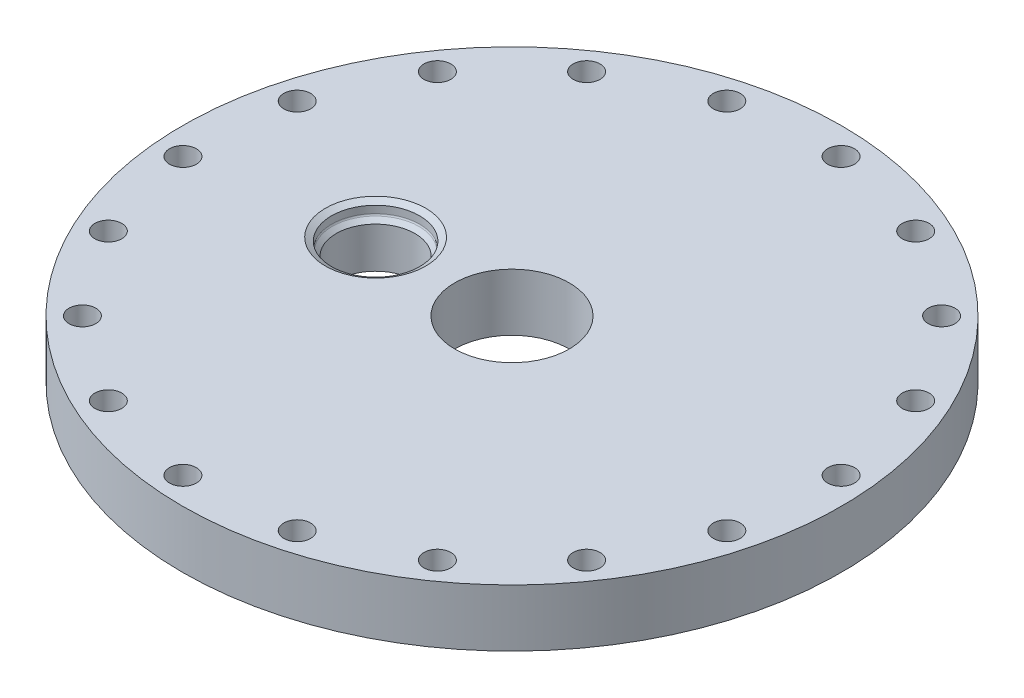
SolidWorks part; units mm, degrees
note: '?' marks a value the reader was unsure of.
material "7075-T6, Plate (SS)"
ref_plane "Front Plane" through (0, 0, 0) normal (0, 0, 1) x (1, 0, 0)
ref_plane "Top Plane" through (0, 0, 0) normal (0, 1, 0) x (1, 0, 0)
ref_plane "Right Plane" through (0, 0, 0) normal (1, 0, 0) x (0, 0, -1)
sketch "Top Plate Diameter" plane through (0, 0, 0) normal (0, 1, 0) x (1, 0, 0)
  circle A0 centre (0, 0) radius 73.025
  dimension "D1" = 146.05
extrude "Top Plate Extrude" add sketch "Top Plate Diameter" along normal blind 12.7
ref_axis "Center of Top Plate" through (0, 12.7, 0) along (0, -1, 0)?
sketch "Fuel Port Clearance Diameter" plane through (0, 12.7, 0) normal (0, 1, 0) x (1, 0, 0)
  circle A0 centre (0, 0) radius 12.7
  dimension "D1" = 25.4
extrude "Fuel Port Clearance Hole" cut sketch "Fuel Port Clearance Diameter" against normal through all
hole_wizard "3/4-16 Tapped LOX Port" [suppressed] positions "3DSketch3" profile "Sketch6" tap size "3/4-16" standard "Ansi Inch"
sketch3d "3DSketch3"
  line L0 (0, 0, 0) -> (0, 37.9824, 0) construction
  point P0 (-30.226, 8.89, 0)
  dimension "D2" = 30.226
sketch "Sketch6" plane through (-30.226, 8.89, 0) normal (1, 0, 0) x (0, 0, 1)
  line L0 (0, 0) -> (0, 17.9463)
  line L1 (0, 17.9463) -> (8.7312, 12.7)
  line L2 (8.7312, 12.7) -> (8.7312, 0)
  line L5 (8.7312, 0) -> (0, 0)
  line L10 (0, 17.9463) -> (-8.7312, 12.7) construction
  line L11 (0, -6.35) -> (0, 107.95) construction
  dimension "Tap Drill Dia." = 17.4625
  dimension "Tap Drill Depth" = 12.7
  dimension "Drill Angle" = 118
cosmetic thread "Hole Thread2" [suppressed] parameters "D1"=38.1, "D2"=19.05
ref_plane "Assembly Bolt Offset Angle" through (0, 0, 0) normal (-0.2588, 0, 0.9659) x (0.9659, 0, 0.2588)
sketch "Assembly Bolt Diameter" plane through (0, 12.7, 0) normal (0, 1, 0) x (1, 0, 0)
  line L0 (-6.747, 1.8079) -> (6.747, -1.8079) construction
  circle A0 centre (-65.0165, 17.4211) radius 2.9769
  dimension "D1" = 5.9538
  dimension "D2" = 67.31
extrude "Assembly Bolt" cut sketch "Assembly Bolt Diameter" against normal up to next
pattern_circular "CirPattern1" count 18 over 360 about axis through (0, 0, 0) along (0, 1, 0) of "Assembly Bolt"
sketch "Sketch7" plane through (0, 12.7, 0) normal (0, 1, 0) x (1, 0, 0)
  line L0 (-6.985, 0) -> (6.985, 0) construction
  circle A0 centre (-30.226, 0) radius 8.7122
  dimension "D1" = 30.226
  dimension "D2" = 17.4244
extrude "LOX Port" cut sketch "Sketch7" against normal up to next
cosmetic thread "Cosmetic Thread1" parameters "D2"=19.05
cosmetic thread "Cosmetic Thread2" parameters "D2"=19.05
sketch "Sketch9" plane through (0, 0, 0) normal (0, 0, 1) x (1, 0, 0)
  line L0 (-30.226, 12.7) -> (-21.5138, 3.658) construction
  line L1 (-21.5138, 3.658) -> (-21.5138, 12.7) construction
  line L2 (-21.5138, 12.7) -> (-38.9382, 12.7) construction
  line L4 (-30.226, -7.4689) -> (-30.226, 31.4539) construction
  line L5 (-38.9382, 3.81) -> (-38.9382, 12.7) construction
  line L6 (-30.226, 12.7) -> (-38.9382, 3.81) construction
  line L7 (-41.3385, 12.7) -> (-39.9923, 11.9228)
  line L8 (-39.9923, 11.9228) -> (-39.9923, 10.3124)
  line L9 (-39.8435, 9.9532) -> (-38.9382, 9.0479)
  line L10 (-38.9382, 9.0479) -> (-38.9382, 12.7)
  line L11 (-38.9382, 12.7) -> (-41.3385, 12.7)
  line L12 (73.025, 12.7) -> (-73.025, 12.7) construction
  arc A0 (-39.8435, 9.9532) -> (-39.9923, 10.3124) centre (-39.4843, 10.3124) cw
  dimension "D4" = 0.508
  dimension "D1" = 45
  dimension "D2" = 11.1125
  dimension "D3" = 9.7663
  dimension "D5" = 2.3876
  dimension "D6" = 30
  dimension "D7" = 3.6521
  dimension "D8" = 2.4003
  dimension "D9" = 1.6104
  dimension "D10" = 0.9053
  dimension "D11" = 30.226
revolve "Cut-Revolve1" cut sketch "Sketch9" angle 360 about L4
thread "Thread1" [suppressed] pitch 1.5875 start angle 0, offset 0, length 0, pitch 1.5875, diameter 17.4244
ref_plane "Plane1" through (-37.2872, 9.0479, 0) normal (0, 0, 1) x (-1, 0, 0)
sketch "Thread Profile1" plane through (-37.2872, 9.0479, 0) normal (0, 0, 1) x (-1, 0, 0)
  line L0 (0, 0) -> (0, 1.5875) construction
  line L1 (0, 0) -> (0.8593, 0.4961)
  line L2 (0.8593, 0.4961) -> (0.8593, 0.6945)
  line L3 (0.8593, 0.6945) -> (0, 1.1906)
  line L4 (0.8593, 0.5953) -> (0, 0.5953) construction
  line L11 (0, 0) -> (0, 1.1906)
  point P2 (0, 0)
  dimension "Pitch" = 1.5875
  dimension "Profile_Angle" = 60
  dimension "Profile_Land" = 0.1984
  dimension "Profile_Height" = 0.8593
sketch "Sketch10" plane through (0, 0, 0) normal (0, 1, 0) x (1, 0, 0)
  circle A0 centre (0, 0) radius 52.4383
  circle A1 centre (0, 0) radius 49.8729
  dimension "D1" = 104.8766
  dimension "D2" = 99.7458
split line "Split Line1" [suppressed]
